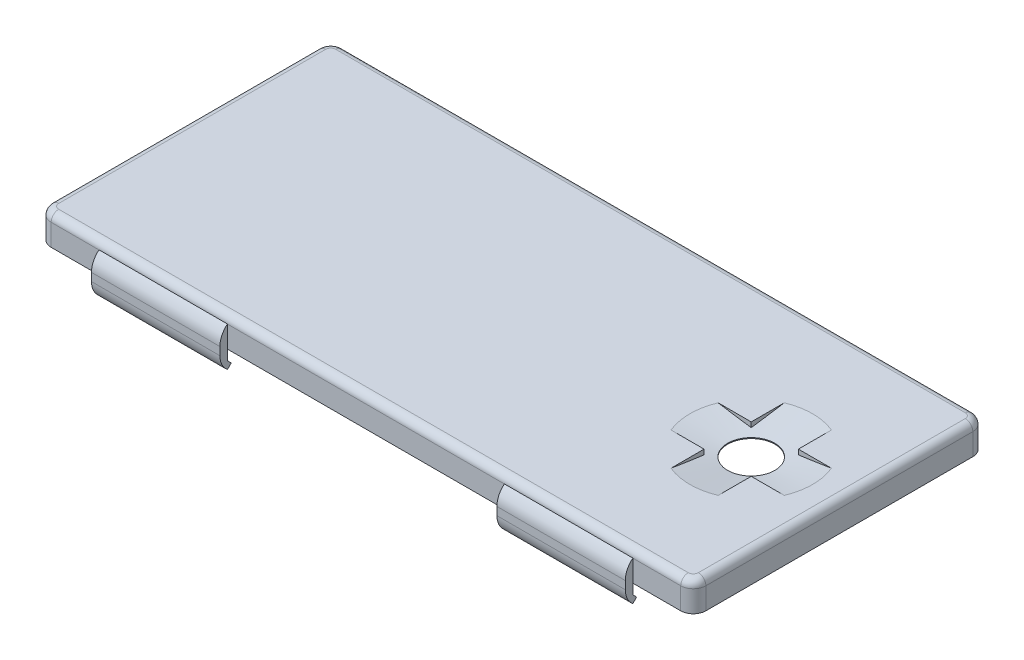
SolidWorks part; units mm, degrees
ref_plane "Front Plane" through (0, 0, 0) normal (0, 0, 1) x (1, 0, 0)
ref_plane "Top Plane" through (0, 0, 0) normal (0, 1, 0) x (1, 0, 0)
ref_plane "Right Plane" through (0, 0, 0) normal (1, 0, 0) x (0, 0, -1)
sketch "Sketch1" plane through (0, 0, 0) normal (0, 1, 0) x (1, 0, 0)
  line L1 (0, 0) -> (260, 0)
  line L2 (0, 0) -> (0, 116)
  line L3 (0, 116) -> (260, 116)
  line L4 (260, 0) -> (260, 116)
  dimension "D1" = 260
  dimension "D2" = 116
extrude "Boss-Extrude1" add sketch "Sketch1" along normal blind 11.62
fillet "Fillet1" radius 5 4 edges at (0, 5.81, 0) (260, 5.81, 0) (260, 5.81, -116) (0, 5.81, -116)
fillet "Fillet2" radius 3 8 edges at (258.5355, 11.62, -114.5355) (260, 11.62, -58) (258.5355, 11.62, -1.4645) (130, 11.62, 0) (1.4645, 11.62, -1.4645) (0, 11.62, -58) (1.4645, 11.62, -114.5355) (130, 11.62, -116)
sketch "Sketch2" plane through (0, 0, 0) normal (0, -1, 0) x (1, 0, 0)
  line L0 (0, -111) -> (0, -5) construction
  line L1 (3, -3) -> (257, -3)
  line L2 (3, -3) -> (3, -113)
  line L3 (3, -113) -> (257, -113)
  line L4 (257, -3) -> (257, -113)
  line L5 (5, 0) -> (255, 0) construction
  line L6 (255, -116) -> (5, -116) construction
  line L7 (260, -5) -> (260, -111) construction
  dimension "D1" = 3
  dimension "D2" = 3
  dimension "D3" = 3
  dimension "D4" = 3
extrude "Cut-Extrude1" cut sketch "Sketch2" against normal blind 8.62
fillet "Fillet3" radius 3 4 edges at (3, 4.31, -113) (257, 4.31, -113) (257, 4.31, -3) (3, 4.31, -3)
sketch "Sketch4" plane through (0, 11.62, 0) normal (0, 1, 0) x (1, 0, 0)
  line L0 (260, 111) -> (260, 5) construction
  line L1 (98.964, 66.4905) -> (198.024, 66.4905)
  line L2 (98.964, 66.4905) -> (98.964, 30.4905)
  line L3 (98.964, 30.4905) -> (198.024, 30.4905)
  line L4 (198.024, 66.4905) -> (198.024, 30.4905)
  dimension "D1" = 36
  dimension "D2" = 99.06
  dimension "D3" = 61.976
sketch "Sketch6" plane through (0, 11.62, 0) normal (0, 1, 0) x (1, 0, 0)
  line L0 (5, 116) -> (255, 116) construction
  line L1 (260, 111) -> (260, 5) construction
  circle A0 centre (225, 58) radius 9.3599
  dimension "D1" = 58
  dimension "D2" = 35
  dimension "D3" = 18.7198
extrude "Cut-Extrude4" cut sketch "Sketch6" against normal blind 8.636
sketch "Sketch7" plane through (0, 0, 0) normal (0, 0, 1) x (1, 0, 0)
  line L0 (5, 0) -> (255, 0) construction
  line L1 (24, 8.6491) -> (75, 8.6491)
  line L2 (24, 8.6491) -> (24, -7)
  line L3 (24, -7) -> (75, -7)
  line L4 (75, 8.6491) -> (75, -7)
  line L5 (0, 0) -> (0, 8.62) construction
  dimension "D1" = 7
  dimension "D2" = 51
  dimension "D3" = 24
extrude "Boss-Extrude3" add sketch "Sketch7" along normal blind 3
fillet "Fillet6" radius 8 1 edges at (49.5, 8.6491, 3)
fillet "Fillet7" radius 8 1 edges at (49.5, -7, 3)
sketch "Sketch8" plane through (0, 0, 0) normal (0, 0, -1) x (-1, 0, 0)
  line L0 (-75, -7) -> (-75, 0) construction
  line L1 (-75, -4) -> (-24, -4)
  line L2 (-75, -4) -> (-75, -7)
  line L3 (-75, -7) -> (-24, -7)
  line L4 (-24, -4) -> (-24, -7)
  dimension "D1" = 3
extrude "Boss-Extrude4" add sketch "Sketch8" along normal blind 1.5
sketch "Sketch9" plane through (24, 0, 0) normal (-1, 0, 0) x (0, 0, 1)
  line L0 (0, -4) -> (-1.5, -5.5)
  line L1 (-1.5, -7) -> (-1.5, -4) construction
  line L2 (-1.5, -5.5) -> (0, -7)
  line L3 (0, -7) -> (-1.5, -7)
  line L4 (-1.5, -7) -> (0, -7) construction
  line L5 (-1.5, -4) -> (-2.0534, -4)
  line L6 (-1.5, -4) -> (0, -4)
  line L7 (-2.0534, -4) -> (-2.0534, -7)
  line L8 (-2.0534, -7) -> (-1.5, -7)
extrude "Cut-Extrude5" cut sketch "Sketch9" against normal blind 55
pattern_linear "LPattern2" count 2 spacing 161 along (1, 0, 0) of "Boss-Extrude3", "Cut-Extrude5", "Boss-Extrude4", "Fillet7", "Fillet6"
sketch "Sketch10" plane through (0, 0, -116) normal (0, 0, -1) x (-1, 0, 0)
  line L0 (0, 8.62) -> (0, 0) construction
  line L1 (-75, 8.62) -> (-24, 8.62)
  line L2 (-75, 8.62) -> (-75, -7)
  line L3 (-75, -7) -> (-24, -7)
  line L4 (-24, 8.62) -> (-24, -7)
  line L5 (-75, 0) -> (-24, 0) construction
  line L6 (-5, 8.62) -> (-255, 8.62) construction
  dimension "D1" = 24
  dimension "D2" = 7
  dimension "D3" = 0
  dimension "D4" = 51
extrude "Boss-Extrude5" add sketch "Sketch10" along normal blind 3
fillet "Fillet8" radius 8 2 edges at (49.5, -7, -119) (49.5, 8.62, -119)
sketch "Sketch11" plane through (0, 0, -116) normal (0, 0, 1) x (1, 0, 0)
  line L0 (24, -7) -> (24, 0) construction
  line L1 (24, -4) -> (75, -4)
  line L2 (24, -4) -> (24, -7)
  line L3 (24, -7) -> (75, -7)
  line L4 (75, -4) -> (75, -7)
  dimension "D1" = 3
extrude "Boss-Extrude6" add sketch "Sketch11" along normal blind 1.5
sketch "Sketch12" plane through (24, 0, 0) normal (-1, 0, 0) x (0, 0, 1)
  line L0 (-116, -4) -> (-114.5, -5.5)
  line L1 (-114.5, -4) -> (-114.5, -7) construction
  line L2 (-114.5, -5.5) -> (-116, -7)
  line L3 (-116, -7) -> (-111.986, -7)
  line L4 (-111.986, -7) -> (-111.986, -3.7983)
  line L5 (-111.986, -3.7983) -> (-116, -4)
extrude "Cut-Extrude6" cut sketch "Sketch12" against normal blind 55
pattern_linear "LPattern3" count 2 spacing 161 along (1, 0, 0) of "Boss-Extrude5", "Cut-Extrude6", "Boss-Extrude6", "Fillet8"
chamfer "Chamfer1" distance 15 angle 10 1 edges at (225, 11.62, -48.6401) first distance on face at (225, 11.62, -48.6401)
sketch "Sketch13" plane through (0, 11.62, 0) normal (0, 1, 0) x (1, 0, 0)
  line L6 (253.194, 67.36) -> (234.36, 67.36)
  line L7 (215.64, 67.36) -> (192.0999, 67.36)
  line L8 (215.64, 67.36) -> (215.64, 93.3614)
  line L9 (215.64, 93.3614) -> (192.0999, 93.3614)
  line L10 (192.0999, 67.36) -> (192.0999, 93.3614)
  line L11 (253.194, 67.36) -> (253.194, 94.5157)
  line L12 (253.194, 94.5157) -> (234.36, 94.5157)
  line L13 (234.36, 67.36) -> (234.36, 94.5157)
  line L15 (247.7709, 29.8831) -> (234.36, 29.8831)
  line L16 (247.7709, 29.8831) -> (247.7709, 48.64)
  line L17 (247.7709, 48.64) -> (234.36, 48.64)
  line L18 (234.36, 29.8831) -> (234.36, 48.64)
  line L19 (200.2954, 32.3234) -> (215.64, 32.3234)
  line L20 (200.2954, 32.3234) -> (200.2954, 48.64)
  line L21 (200.2954, 48.64) -> (215.64, 48.64)
  line L22 (215.64, 32.3234) -> (215.64, 48.64)
extrude "Boss-Extrude7" add sketch "Sketch13" against normal blind 3
